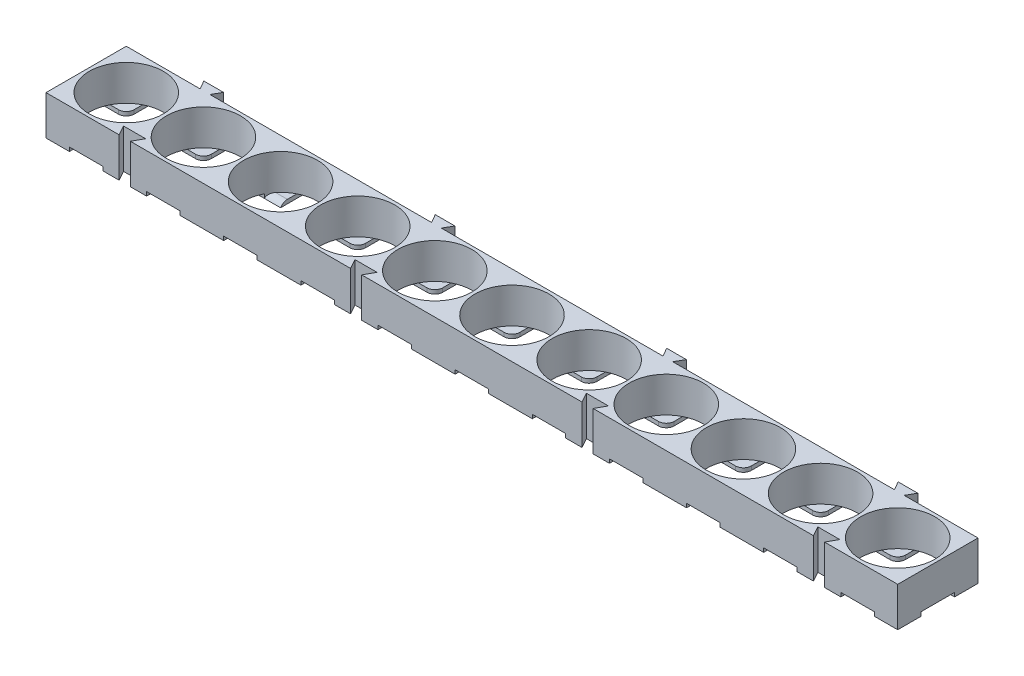
SolidWorks part; units mm, degrees
ref_plane "Front Plane" through (0, 0, 0) normal (0, 0, 1) x (1, 0, 0)
ref_plane "Top Plane" through (0, 0, 0) normal (0, 1, 0) x (1, 0, 0)
ref_plane "Right Plane" through (0, 0, 0) normal (1, 0, 0) x (0, 0, -1)
sketch "Sketch3" plane through (0, 0, 0) normal (0, 1, 0) x (1, 0, 0)
  line L0 (-10.2, 0) -> (9.4, 0) construction
  line L5 (9.4, 9.4) -> (9.4, -9.4) construction
  line L6 (9.4, -9.4) -> (-9.4, -9.4) construction
  line L7 (-9.4, -9.4) -> (-9.4, 9.4) construction
  line L8 (-9.4, 9.4) -> (9.4, 9.4) construction
  line L9 (10.2, -9.4) -> (10.2, 9.4) construction
  line L10 (10.2, 9.4) -> (29, 9.4) construction
  line L11 (29, 9.4) -> (29, -9.4) construction
  line L12 (29, -9.4) -> (10.2, -9.4) construction
  line L13 (29.8, -9.4) -> (29.8, 9.4) construction
  line L14 (29.8, 9.4) -> (48.6, 9.4) construction
  line L15 (48.6, 9.4) -> (48.6, -9.4) construction
  line L16 (48.6, -9.4) -> (29.8, -9.4) construction
  line L17 (49.4, -9.4) -> (49.4, 9.4) construction
  line L18 (49.4, 9.4) -> (68.2, 9.4) construction
  line L19 (68.2, 9.4) -> (68.2, -9.4) construction
  line L20 (68.2, -9.4) -> (49.4, -9.4) construction
  line L21 (69, -9.4) -> (69, 9.4) construction
  line L22 (69, 9.4) -> (87.8, 9.4) construction
  line L23 (87.8, 9.4) -> (87.8, -9.4) construction
  line L24 (87.8, -9.4) -> (69, -9.4) construction
  line L25 (88.6, -9.4) -> (88.6, 9.4) construction
  line L26 (88.6, 9.4) -> (107.4, 9.4) construction
  line L27 (107.4, 9.4) -> (107.4, -9.4) construction
  line L28 (107.4, -9.4) -> (88.6, -9.4) construction
  line L29 (108.2, -9.4) -> (108.2, 9.4) construction
  line L30 (108.2, 9.4) -> (127, 9.4) construction
  line L31 (127, 9.4) -> (127, -9.4) construction
  line L32 (127, -9.4) -> (108.2, -9.4) construction
  line L33 (127.8, -9.4) -> (127.8, 9.4) construction
  line L34 (127.8, 9.4) -> (146.6, 9.4) construction
  line L35 (146.6, 9.4) -> (146.6, -9.4) construction
  line L36 (146.6, -9.4) -> (127.8, -9.4) construction
  line L37 (147.4, -9.4) -> (147.4, 9.4) construction
  line L38 (147.4, 9.4) -> (166.2, 9.4) construction
  line L39 (166.2, 9.4) -> (166.2, -9.4) construction
  line L40 (166.2, -9.4) -> (147.4, -9.4) construction
  line L41 (167, -9.4) -> (167, 9.4) construction
  line L42 (167, 9.4) -> (185.8, 9.4) construction
  line L43 (185.8, 9.4) -> (185.8, -9.4) construction
  line L44 (185.8, -9.4) -> (167, -9.4) construction
  line L45 (186.6, -9.4) -> (186.6, 9.4) construction
  line L46 (186.6, 9.4) -> (205.4, 9.4) construction
  line L47 (205.4, 9.4) -> (205.4, -9.4) construction
  line L48 (205.4, -9.4) -> (186.6, -9.4) construction
  line L49 (-10.2, 0) -> (206.2, 0) construction
  line L50 (-10.2, 10.2) -> (206.2, 10.2)
  line L51 (-10.2, 10.2) -> (-10.2, -10.2)
  line L52 (-10.2, -10.2) -> (206.2, -10.2)
  line L53 (206.2, 10.2) -> (206.2, -10.2)
  line L54 (9.4, 9.4) -> (10.2, 9.4) construction
  line L55 (9.8, 29) -> (9.8, -10.2) construction
  line L56 (68.2, 9.4) -> (69, 9.4) construction
  line L57 (68.6, 9.4) -> (68.6, 13.7208) construction
  line L58 (12.3, 12.4) -> (7.3, 12.4)
  line L59 (7.3, 12.4) -> (8.5702, 10.2)
  line L60 (8.5702, 10.2) -> (11.0298, 10.2)
  line L61 (12.3, 12.4) -> (11.0298, 10.2)
  line L62 (12.6, -7.7) -> (7, -7.7)
  line L63 (7, -7.7) -> (8.3858, -10.2)
  line L64 (8.3858, -10.2) -> (11.2142, -10.2)
  line L65 (12.6, -7.7) -> (11.2142, -10.2)
  line L66 (67.3702, 10.2) -> (69.8298, 10.2)
  line L67 (71.1, 12.4) -> (69.8298, 10.2)
  line L68 (71.1, 12.4) -> (66.1, 12.4)
  line L69 (66.1, 12.4) -> (67.3702, 10.2)
  line L70 (67.1858, -10.2) -> (70.0142, -10.2)
  line L71 (71.4, -7.7) -> (70.0142, -10.2)
  line L72 (71.4, -7.7) -> (65.8, -7.7)
  line L73 (65.8, -7.7) -> (67.1858, -10.2)
  line L74 (126.1702, 10.2) -> (128.6298, 10.2)
  line L75 (129.9, 12.4) -> (128.6298, 10.2)
  line L76 (129.9, 12.4) -> (124.9, 12.4)
  line L77 (124.9, 12.4) -> (126.1702, 10.2)
  line L78 (125.9858, -10.2) -> (128.8142, -10.2)
  line L79 (130.2, -7.7) -> (128.8142, -10.2)
  line L80 (130.2, -7.7) -> (124.6, -7.7)
  line L81 (124.6, -7.7) -> (125.9858, -10.2)
  line L82 (184.9702, 10.2) -> (187.4298, 10.2)
  line L83 (188.7, 12.4) -> (187.4298, 10.2)
  line L84 (188.7, 12.4) -> (183.7, 12.4)
  line L85 (183.7, 12.4) -> (184.9702, 10.2)
  line L86 (184.7858, -10.2) -> (187.6142, -10.2)
  line L87 (189, -7.7) -> (187.6142, -10.2)
  line L88 (189, -7.7) -> (183.4, -7.7)
  line L89 (183.4, -7.7) -> (184.7858, -10.2)
  line L90 (68.6, 12.4) -> (68.6, 10.2) construction
  circle A0 centre (0, 0) radius 9.4
  circle A1 centre (19.6, 0) radius 9.4
  circle A2 centre (39.2, 0) radius 9.4
  circle A3 centre (58.8, 0) radius 9.4
  circle A4 centre (78.4, 0) radius 9.4
  circle A5 centre (98, 0) radius 9.4
  circle A6 centre (117.6, 0) radius 9.4
  circle A7 centre (137.2, 0) radius 9.4
  circle A8 centre (156.8, 0) radius 9.4
  circle A9 centre (176.4, 0) radius 9.4
  circle A10 centre (196, 0) radius 9.4
  point P10 (-0.4, 0)
  point P13 (-9.4, 0)
  point P16 (0, 9.4)
  point P84 (9.8, 9.4)
  point P88 (9.8, 10.2)
  point P89 (9.8, 12.4)
  point P94 (9.8, -7.7)
  dimension "D1" = 18.8
  dimension "D2" = 11
  dimension "D3" = 0.8
  dimension "D4" = 0.8
  dimension "D5" = 0.8
  dimension "D6" = 0.8
  dimension "D7" = 216.4
  dimension "D8" = 20.4
  dimension "D9" = 5
  dimension "D10" = 60
  dimension "D11" = 2.2
  dimension "D12" = 5.6
  dimension "D13" = 61
  dimension "D14" = 2.5
  dimension "D15" = 4
extrude "Boss-Extrude3" add sketch "Sketch3" along normal blind 10 contours L89 L88 L87 L52 L53 L50 L51 L63 L62 L65 L73 L72 L71 L81 L80 L79 A10 A9 A8 A7 A6 A5 A4 A3 A2 A1 A0 | L61 L58 L59 L50 | L68 L69 L50 L67 | L76 L77 L50 L75 | L84 L85 L50 L83 region at (-0.8149, 0, -9.9826) region at (9.8, 0, -11.4249) region at (68.6, 0, -11.4249) region at (127.4, 0, -11.4249) region at (186.2, 0, -11.4249)
extrude "Boss-Extrude6" add sketch "Sketch3<4>" along normal blind 1 contours A0 | A1 | A2 | A3 | A4 | A5 | A6 | A7 | A8 | A9 | A10 region at (0, 0, 0) region at (19.6, 0, 0) region at (39.2, 0, 0) region at (58.8, 0, 0) region at (78.4, 0, 0) region at (98, 0, 0) region at (117.6, 0, 0) region at (137.2, 0, 0) region at (156.8, 0, 0) region at (176.4, 0, 0) region at (196, 0, 0)
sketch "Sketch3<4>" plane through (0, 0, 0) normal (0, 1, 0) x (1, 0, 0) same geometry as "Sketch3"
sketch "Sketch8" plane through (0, 1, 0) normal (0, 1, 0) x (1, 0, 0)
  line L0 (-9.4, 0) -> (9.4, 0) construction
  line L1 (0, -9.4) -> (0, 9.4) construction
  line L2 (19.6, -9.4) -> (19.6, 9.4) construction
  line L3 (206.2, 10.2) -> (206.2, -10.2) construction
  line L4 (-10.2, -4.25) -> (206.2, -4.25)
  line L5 (-10.2, -4.25) -> (-10.2, 4.25)
  line L6 (-10.2, 4.25) -> (206.2, 4.25)
  line L7 (206.2, -4.25) -> (206.2, 4.25)
  line L8 (-10.2, -4.25) -> (206.2, 4.25) construction
  line L9 (-10.2, 4.25) -> (206.2, -4.25) construction
  line L10 (-10.2, 10.2) -> (8.5702, 10.2) construction
  line L11 (-4.25, -10.2) -> (4.25, -10.2)
  line L12 (-4.25, -10.2) -> (-4.25, 10.2)
  line L13 (-4.25, 10.2) -> (4.25, 10.2)
  line L14 (4.25, -10.2) -> (4.25, 10.2)
  line L15 (-4.25, -10.2) -> (4.25, 10.2) construction
  line L16 (-4.25, 10.2) -> (4.25, -10.2) construction
  line L17 (15.35, -10.2) -> (15.35, 10.2)
  line L18 (15.35, -10.2) -> (23.85, -10.2)
  line L19 (23.85, -10.2) -> (23.85, 10.2)
  line L20 (15.35, 10.2) -> (23.85, 10.2)
  line L21 (34.95, -10.2) -> (34.95, 10.2)
  line L22 (34.95, -10.2) -> (43.45, -10.2)
  line L23 (43.45, -10.2) -> (43.45, 10.2)
  line L24 (34.95, 10.2) -> (43.45, 10.2)
  line L25 (54.55, -10.2) -> (54.55, 10.2)
  line L26 (54.55, -10.2) -> (63.05, -10.2)
  line L27 (63.05, -10.2) -> (63.05, 10.2)
  line L28 (54.55, 10.2) -> (63.05, 10.2)
  line L29 (74.15, -10.2) -> (74.15, 10.2)
  line L30 (74.15, -10.2) -> (82.65, -10.2)
  line L31 (82.65, -10.2) -> (82.65, 10.2)
  line L32 (74.15, 10.2) -> (82.65, 10.2)
  line L33 (93.75, -10.2) -> (93.75, 10.2)
  line L34 (93.75, -10.2) -> (102.25, -10.2)
  line L35 (102.25, -10.2) -> (102.25, 10.2)
  line L36 (93.75, 10.2) -> (102.25, 10.2)
  line L37 (113.35, -10.2) -> (113.35, 10.2)
  line L38 (113.35, -10.2) -> (121.85, -10.2)
  line L39 (121.85, -10.2) -> (121.85, 10.2)
  line L40 (113.35, 10.2) -> (121.85, 10.2)
  line L41 (132.95, -10.2) -> (132.95, 10.2)
  line L42 (132.95, -10.2) -> (141.45, -10.2)
  line L43 (141.45, -10.2) -> (141.45, 10.2)
  line L44 (132.95, 10.2) -> (141.45, 10.2)
  line L45 (152.55, -10.2) -> (152.55, 10.2)
  line L46 (152.55, -10.2) -> (161.05, -10.2)
  line L47 (161.05, -10.2) -> (161.05, 10.2)
  line L48 (152.55, 10.2) -> (161.05, 10.2)
  line L49 (172.15, -10.2) -> (172.15, 10.2)
  line L50 (172.15, -10.2) -> (180.65, -10.2)
  line L51 (180.65, -10.2) -> (180.65, 10.2)
  line L52 (172.15, 10.2) -> (180.65, 10.2)
  line L53 (191.75, -10.2) -> (191.75, 10.2)
  line L54 (191.75, -10.2) -> (200.25, -10.2)
  line L55 (200.25, -10.2) -> (200.25, 10.2)
  line L56 (191.75, 10.2) -> (200.25, 10.2)
  line L57 (15.35, 10.2) -> (23.85, -10.2) construction
  circle A2 centre (0, 0) radius 9.4
  circle A3 centre (0, 0) radius 9.4 construction
  circle A5 centre (19.6, 0) radius 9.4
  circle A6 centre (19.6, 0) radius 9.4 construction
  point P3 (0, 0)
  point P12 (0, 0)
  point P14 (19.6, 0)
  point P15 (98, 0)
  point P29 (0, 0)
  dimension "D3" = 19.6
  dimension "D4" = 8.5
  dimension "D5" = 11
  dimension "D1" = 0
  dimension "D2" = 0
extrude "Cut-Extrude4" cut sketch "Sketch8" against normal through all contours L6 L7 L4 L5 | L12 L13 L14 L11 | L17 L20 L19 L18 | L21 L24 L23 L22 | L25 L28 L27 L26 | L29 L32 L31 L30 | L33 L36 L35 L34 | L37 L40 L39 L38 | L41 L44 L43 L42 | L45 L48 L47 L46 | L49 L52 L51 L50 | L53 L56 L55 L54
fillet "Fillet3" radius 2 44 edges at (4.25, 0.5, -4.25) (-4.25, 0.5, -4.25) (4.25, 0.5, 4.25) (-4.25, 0.5, 4.25) (191.75, 0.5, -4.25) (191.75, 0.5, 4.25) (172.15, 0.5, -4.25) (172.15, 0.5, 4.25) (152.55, 0.5, 4.25) (152.55, 0.5, -4.25) (132.95, 0.5, -4.25) (132.95, 0.5, 4.25) (113.35, 0.5, -4.25) (111.2828, 1, 4.25) (93.75, 0.5, 4.25) (93.75, 0.5, -4.25) (74.15, 0.5, 4.25) (74.15, 0.5, -4.25) (54.55, 0.5, -4.25) (54.55, 0.5, 4.25) (34.95, 0.5, 4.25) (32.8828, 1, -4.25) (63.05, 0.5, -4.25) (63.05, 0.5, 4.25) (82.65, 0.5, -4.25) (82.65, 0.5, 4.25) (102.25, 0.5, -4.25) (102.25, 0.5, 4.25) (121.85, 0.5, -4.25) (121.85, 0.5, 4.25) (141.45, 0.5, 4.25) (141.45, 0.5, -4.25) (161.05, 0.5, -4.25) (161.05, 0.5, 4.25) (180.65, 0.5, 4.25) (180.65, 0.5, -4.25) (200.25, 0.5, -4.25) (200.25, 0.5, 4.25) (43.45, 0.5, 4.25) (43.45, 0.5, -4.25) (23.85, 0.5, -4.25) (23.85, 0.5, 4.25) (15.35, 0.5, 4.25) (15.35, 0.5, -4.25)
equation "\"`\"=10"
